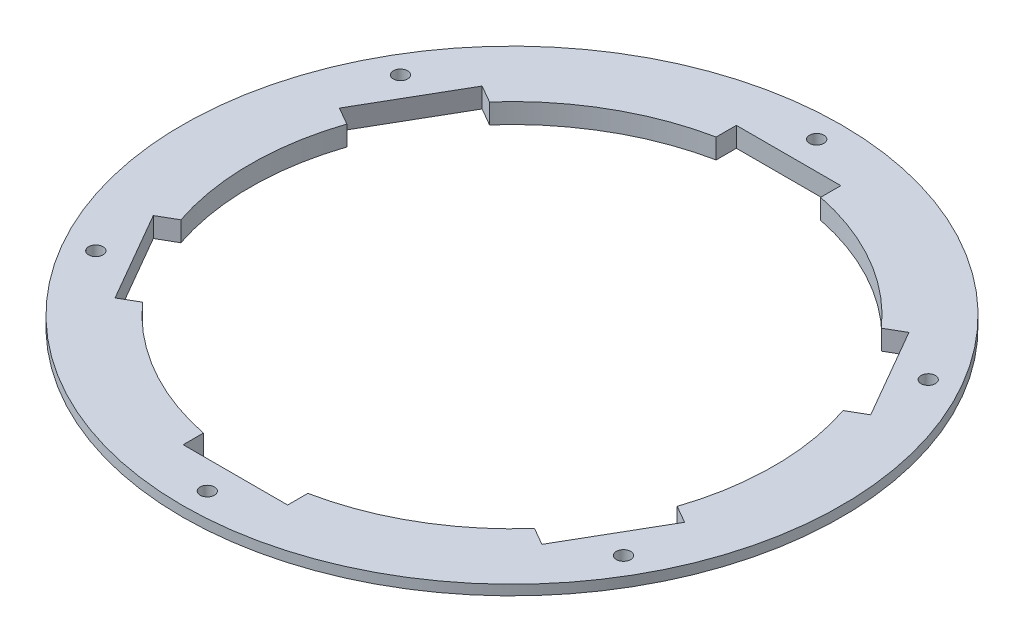
SolidWorks part; units mm, degrees
material "6061 Alloy"
ref_plane "Front Plane" through (0, 0, 0) normal (0, 0, 1) x (1, 0, 0)
ref_plane "Top Plane" through (0, 0, 0) normal (0, 1, 0) x (1, 0, 0)
ref_plane "Right Plane" through (0, 0, 0) normal (1, 0, 0) x (0, 0, -1)
sketch "Sketch1" plane through (0, 0, 0) normal (0, 1, 0) x (1, 0, 0)
  line L0 (-13.335, -65.4575) -> (-13.335, -69.3414)
  line L1 (13.335, -65.4575) -> (13.335, -69.3414)
  line L2 (-13.335, -70.612) -> (13.335, -70.612)
  line L3 (13.335, -69.3414) -> (13.335, -70.612)
  line L4 (-13.335, -69.3414) -> (-13.335, -70.612)
  circle A0 centre (0, 0) radius 66.802
  circle A1 centre (0, 0) radius 84.1375
  circle A2 centre (0, 0) radius 70.612
  circle A3 centre (0, -77.7875) radius 1.8288
  dimension "D1" = 133.604
  dimension "D2" = 168.275
  dimension "D8" = 3.6576
  dimension "D4" = 13.335
  dimension "D5" = 13.335
  dimension "D7" = 77.7875
  dimension "D3" = 3.81
extrude "Boss-Extrude1" add sketch "Sketch1" along normal blind 5.08 contours L1 A2 L0 A0 | A1 A2 A0 region at (-15.3232, 0, 67.3995) region at (-81.7577, 0, 0)
pattern_circular "CirPattern1" count 6 over 360 about axis through (0, 5.08, 0) along (0, 1, 0) of face at (-13.335, 2.54, 68.0348) of face at (13.335, 2.54, 68.0348) of face at (0, 5.08, 79.6163) of face at (0, 2.54, 70.612)
sketch "Sketch2" plane through (0, 0, 0) normal (1, 0, 0) x (0, 0, -1)
  line L0 (84.1375, 5.08) -> (-84.1375, 5.08) construction
  line L1 (-84.1375, 0) -> (84.1375, 0) construction
  line L2 (84.1375, 5.08) -> (-84.1375, 5.08)
  line L3 (-84.1375, 0) -> (84.1375, 0)
  line L4 (0, 0) -> (0, 5.08) construction
  circle A0 centre (-83.2231, 0) radius 2.667
  dimension "D1" = 5.334
  dimension "D2" = 0.9144
revolve "Cut-Revolve1" cut sketch "Sketch2" angle 360 about L4 region at (0, 0, 85.8147)
sketch "Sketch4" plane through (0, 0, 0) normal (0, -1, 0) x (1, 0, 0)
  line L0 (0, 0) -> (36.9888, -64.0664) construction
  line L1 (0, 0) -> (0, -39.7137) construction
  circle A0 centre (36.9888, -64.0664) radius 5.588
  circle M34 centre (0, 0) radius 80.5561
  dimension "D2" = 11.176
  dimension "D1" = 73.9775
  dimension "D3" = 30
extrude "Cut-Extrude1" cut sketch "Sketch4" against normal blind 1.905 contours A0 M34 region at (36.9888, 0, -64.0664)
pattern_circular "CirPattern2" count 3 over 360 about axis through (0, 0, 0) along (0, 1, 0) of "Cut-Extrude1"
equation "\"Middle Coupler Inner Daimeter\"= 4.75in"
equation "\"Middle Coupler  Wall Thickness\" = 0.25in"
equation "\"Middle Coupler Bottom Thickness\"= 0.2in"
equation "\"Bearing Rail Offset\"= 0.45in"
equation "\"3-56 UNF Tap\"= 0.089in"
equation "\"3-56 UNF Clearance\"= 0.104in"
equation "\"Ball Bearing Distance\"= 0.03in"
equation "\"D1@Sketch1\"=\"Middle Coupler Inner Daimeter\"+0.5+0.005*2in"
equation "\"TCA Outer Diameter\" = 6.625in"
equation "\"D2@Sketch1\"=\"TCA Outer Diameter\""
equation "\"D4@Sketch1\"=0.50 + (0.05/2)"
equation "\"D5@Sketch1\"=\"D4@Sketch1\""
equation "\"D7@Sketch1\"=(\"D2@Sketch1\"-0.5)/2"
equation "\"D8@Sketch1\"=\"6-32 Clearance\""
equation "\"D2@Sketch2\"=\"Interstage Aeroframe Wall Thickness\"/2"
equation "\"Interstage Aeroframe Wall Thickness\" = 0.072in"
equation "\"D1@Sketch4\"=((\"Middle Coupler Inner Daimeter\"+0.625in)/2in+0.225in)"
equation "\"Compression Spring OD\"= 0.42in"
equation "\"10-24 Tap\"= 0.157in"
equation "\"10-24 Clearance\"= 0.196in"
equation "\"D2@Sketch4\"=\"Compression Spring OD\"+0.02"
equation "\"D3@Sketch1\"=0.125in+(0.05/2)"
equation "\"Lower Stage Fuselage Wall Thickness\" = 0.25in"
equation "\"6-32 Tap\" = 0.107in"
equation "\"1/4-20 Tap\" = 0.201in"
equation "\"3-48 Tap\"= 0.079in"
equation "\"12-24 Tap\" = 0.177in"
equation "\"3-48 Clearance\" = 0.104in"
equation "\"6-32 Clearance\" = 0.144"
